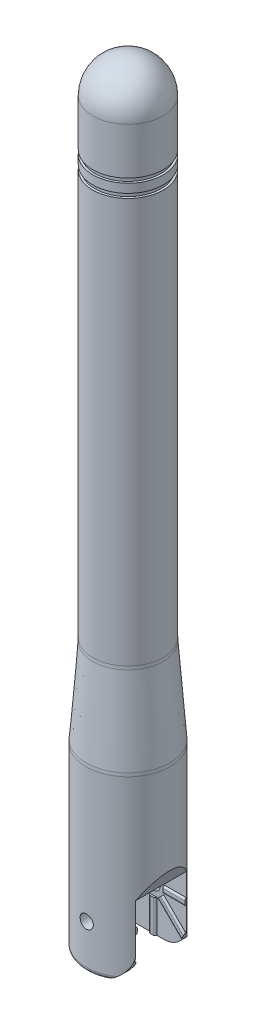
SolidWorks part; units mm, degrees
ref_plane "Plan de face" through (0, 0, 0) normal (0, 0, 1) x (1, 0, 0)
ref_plane "Plan de dessus" through (0, 0, 0) normal (0, 1, 0) x (1, 0, 0)
ref_plane "Plan de droite" through (0, 0, 0) normal (1, 0, 0) x (0, 0, -1)
sketch "Esquisse2" plane through (0, 0, 0) normal (0, 0, 1) x (1, 0, 0)
  line L0 (0, 0) -> (0, 87.9) construction
  line L1 (0, 87.9) -> (4, 87.9) construction
  line L2 (4, 87.9) -> (4, 0) construction
  line L3 (4, 0) -> (0, 0) construction
  line L4 (4, 0) -> (4.75, 0) construction
  line L5 (4.75, 0) -> (4.75, 20.4) construction
  line L6 (4.75, 20.4) -> (0, 20.4) construction
  line L7 (4, 83.9) -> (4, 30.5872) construction
  line L8 (4.014, 30.2133) -> (4.736, 20.5867)
  line L9 (4.75, 20.2128) -> (4.75, 0)
  line L10 (4.75, 0) -> (1, 0)
  line L11 (1, 0) -> (1, 83.9)
  line L12 (1, 83.9) -> (0, 83.9)
  line L13 (4, 83.9) -> (4, 78.6)
  line L14 (4, 78.6) -> (3.75, 78.6)
  line L15 (3.75, 78.6) -> (3.75, 78.1)
  line L16 (3.75, 78.1) -> (4, 78.1)
  line L17 (4, 78.1) -> (4, 77.1)
  line L18 (4, 77.1) -> (3.75, 77.1)
  line L19 (3.75, 77.1) -> (3.75, 76.6)
  line L20 (3.75, 76.6) -> (4, 76.6)
  line L21 (0, 87.9) -> (0, 83.9)
  line L22 (4, 76.6) -> (4, 30.5872)
  arc A0 (0, 87.9) -> (4, 83.9) centre (0, 83.9) cw
  arc A1 (4.75, 20.2128) -> (4.736, 20.5867) centre (-0.25, 20.2128) ccw
  arc A2 (4.014, 30.2133) -> (4, 30.5872) centre (9, 30.5872) cw
  point P18 (4, 30.4)
  point P25 (3.875, 77.1)
  dimension "D7" = 5
  dimension "D1" = 87.9
  dimension "D2" = 8
  dimension "D3" = 9.5
  dimension "D4" = 20.4
  dimension "D5" = 2
  dimension "D6" = 10
  dimension "D8" = 9.3
  dimension "D9" = 0.5
  dimension "D10" = 1.5
  dimension "D11" = 7.5
revolve "Révolution1" add sketch "Esquisse2" angle 360 about L0
sketch "Esquisse3" plane through (0, 0, 0) normal (0, -1, 0) x (1, 0, 0)
  line L0 (0, 0) -> (-2.75, 0) construction
  line L1 (-2.75, 2.9) -> (4.75, 2.9)
  line L2 (-2.75, 2.9) -> (-2.75, -2.9)
  line L3 (-2.75, -2.9) -> (4.75, -2.9)
  line L4 (4.75, 2.9) -> (4.75, -2.9)
  line L5 (-4.75, 0) -> (-2.75, 0) construction
  circle A0 centre (0, 0) radius 4.75 construction
  dimension "D1" = 5.8
  dimension "D2" = 2
extrude "Enlèv. mat.-Extru.1" cut sketch "Esquisse3" against normal blind 8
fillet "Congé1" radius 0.5 1 edges at (-4.75, 0, 0)
sketch "Esquisse4" plane through (0, 0, 0) normal (0, 0, 1) x (1, 0, 0)
  line L0 (3.762, 8) -> (3.762, 0.5) construction
  line L1 (-4.75, 0) -> (3.762, 0) construction
  line L2 (1.162, 0) -> (3.762, 0)
  line L3 (3.762, 0) -> (3.762, 2.6)
  line L4 (0, 0) -> (0, 5) construction
  line L5 (3.762, 8) -> (4.75, 10)
  line L6 (4.75, 8) -> (4.75, 20.2128) construction
  line L7 (4.75, 10) -> (4.75, 8)
  line L8 (3.762, 8) -> (4.75, 8) construction
  line L9 (4.75, 8) -> (3.762, 8)
  arc A0 (3.762, 2.6) -> (1.162, 0) centre (1.162, 2.6) cw
  circle A1 centre (0, 5) radius 0.75
  dimension "D1" = 2.6
  dimension "D3" = 1.5
  dimension "D2" = 5
  dimension "D4" = 2
extrude "Enlèv. mat.-Extru.2" cut sketch "Esquisse4" against normal through all both and the other way through all
sketch "Esquisse5" plane through (0, 0, -2.9) normal (0, 0, 1) x (1, 0, 0)
  line L0 (-4.25, 0) -> (1.162, 0) construction
  line L1 (-0.375, 0) -> (0.375, 0)
  line L2 (-0.375, 0) -> (-0.375, 3.75)
  line L3 (-0.375, 3.75) -> (0.375, 3.75)
  line L4 (0.375, 0) -> (0.375, 3.75)
  line L5 (0, 5) -> (0, 3.75) construction
  line L6 (0, 5) -> (3.762, 1.238) construction
  line L7 (3.762, 8) -> (3.762, 2.6) construction
  line L8 (0.6187, 3.851) -> (3.4968, 0.9729) construction
  line L9 (0.6187, 3.851) -> (1.149, 4.3813)
  line L10 (3.4968, 0.9729) -> (4.0271, 1.5032)
  line L11 (1.149, 4.3813) -> (4.0271, 1.5032) construction
  line L12 (0.6187, 3.851) -> (4.0271, 1.5032) construction
  line L13 (3.4968, 0.9729) -> (1.149, 4.3813) construction
  line L14 (1.149, 4.3813) -> (4.0271, 1.5032)
  line L15 (0.6187, 3.851) -> (3.4968, 0.9729)
  line L16 (0, 5) -> (3.762, 5) construction
  line L18 (1.25, 4.625) -> (3.762, 4.625)
  line L19 (1.25, 4.625) -> (1.25, 5.375)
  line L20 (1.25, 5.375) -> (3.762, 5.375)
  line L21 (3.762, 4.625) -> (3.762, 5.375)
  line L22 (1.25, 4.625) -> (3.762, 5.375) construction
  line L23 (1.25, 5.375) -> (3.762, 4.625) construction
  point P9 (3.762, 1.7804)
  point P13 (2.3229, 2.6771)
  point P14 (3.762, 1.7804)
  point P15 (3.1861, 1.2835)
  point P18 (2.506, 5)
  point P20 (2.1843, 2.8157)
  point P27 (0, 0)
  point P28 (3.762, 5)
  dimension "D1" = 0.75
  dimension "D2" = 1.25
  dimension "D3" = 45
  dimension "D4" = 1.25
  dimension "D5" = 1.25
extrude "Boss.-Extru.1" add sketch "Esquisse5" along normal blind 0.2
fillet "Congé2" radius 0.2 6 edges at (2.506, 5.375, -2.7) (2.506, 4.625, -2.7) (2.5881, 2.9422, -2.7) (2.0578, 2.4119, -2.7) (-0.375, 1.875, -2.7) (0.375, 1.875, -2.7)
mirror "Symétrie1" about plane through (0, 0, 0) normal (0, 0, 1) of "Congé2", "Boss.-Extru.1"
sketch "Esquisse6" plane through (0, 0, 2.9) normal (0, 0, 1) x (1, 0, 0)
  line L3 (4.0271, 1.5032) -> (3.6581, 1.8723)
  line L4 (3.3199, 1.1497) -> (3.4968, 0.9729)
  line L5 (3.4968, 0.9729) -> (4.0271, 1.5032)
  line L6 (4.0271, 1.5032) -> (3.6581, 1.8723)
  line L7 (3.3199, 1.1497) -> (3.4968, 0.9729)
  line L8 (3.4968, 0.9729) -> (4.0271, 1.5032)
  arc A1 (3.3199, 1.1497) -> (3.6581, 1.8723) centre (1.162, 2.6) ccw
  arc A2 (3.3199, 1.1497) -> (3.6581, 1.8723) centre (1.162, 2.6) ccw
  dimension "D1" = 0
extrude "Enlèv. mat.-Extru.3" cut sketch "Esquisse6" against normal through all
